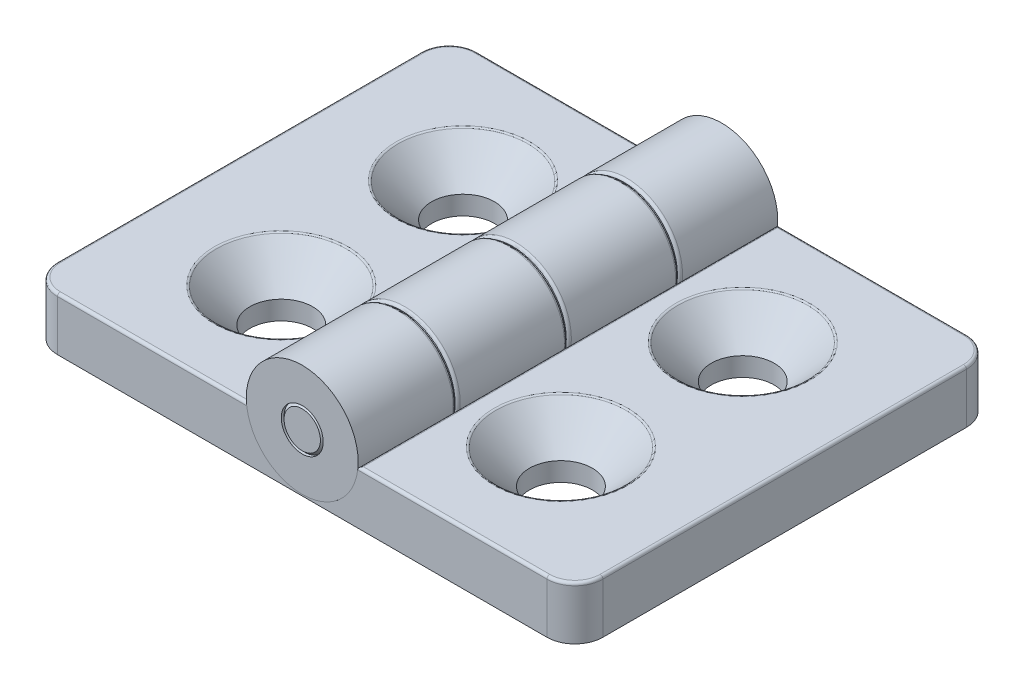
SolidWorks part; units mm, degrees
ref_plane "前视基准面" through (0, 0, 0) normal (0, 0, 1) x (1, 0, 0)
ref_plane "上视基准面" through (0, 0, 0) normal (0, 1, 0) x (1, 0, 0)
ref_plane "右视基准面" through (0, 0, 0) normal (1, 0, 0) x (0, 0, -1)
sketch "草图1" plane through (0, 0, 0) normal (0, 0, 1) x (1, 0, 0)
  circle A0 centre (0, 0) radius 4
  circle A1 centre (0, 0) radius 1.5
  dimension "D1" = 8
  dimension "D2" = 3
extrude "凸台-拉伸1" add sketch "草图1" along normal mid plane 30
sketch "草图2" plane through (0, 0, 0) normal (0, 0, 1) x (1, 0, 0)
  circle A0 centre (0, 0) radius 1.5
  dimension "D1" = 3
extrude "凸台-拉伸2" add sketch "草图2" along normal mid plane 30 separate body
chamfer "倒角1" distance 0.2 angle 45 1 edges at (1.5, 0, 15)
sketch "草图3" plane through (0, 0, 0) normal (0, 1, 0) x (1, 0, 0)
  line L0 (0, 0) -> (14.2235, 0) construction
  line L1 (3.8325, 8) -> (4.8947, 8)
  line L2 (3.8325, 8) -> (3.8325, 7.9)
  line L3 (3.8325, 7.9) -> (4.8947, 7.9)
  line L4 (4.8947, 8) -> (4.8947, 7.9)
  line L5 (4, 15) -> (-4, 15) construction
  line L6 (-4, -15) -> (4, -15) construction
  line L9 (3.8325, 0.05) -> (4.8947, 0.05)
  line L10 (3.8325, 0.05) -> (3.8325, -0.05)
  line L11 (3.8325, -0.05) -> (4.8947, -0.05)
  line L12 (4.8947, 0.05) -> (4.8947, -0.05)
  line L13 (3.8325, -7.9) -> (4.8947, -7.9)
  line L14 (3.8325, -7.9) -> (3.8325, -8)
  line L15 (3.8325, -8) -> (4.8947, -8)
  line L16 (4.8947, -7.9) -> (4.8947, -8)
  point P4 (3.8325, 0)
  dimension "D1" = 7
  dimension "D2" = 0.1
  dimension "D3" = 7
revolve "切除-旋转1" cut sketch "草图3" angle 360 about axis through (0, 0, 15) along (0, 0, -1)
fillet "圆角1" radius 0.2 6 edges at (4, 0, 8) (-4, 0, 7.9) (4, 0, 0.05) (-4, 0, -0.05) (4, 0, -7.9) (-4, 0, -8)
sketch "草图4" plane through (0, 0, 0) normal (0, 1, 0) x (1, 0, 0)
  line L0 (-4, -15) -> (4, -15) construction
  line L1 (-19.5, 15) -> (19.5, 15)
  line L2 (-19.5, 15) -> (-19.5, -15)
  line L3 (-19.5, -15) -> (19.5, -15)
  line L4 (19.5, 15) -> (19.5, -15)
  line L5 (4, 15) -> (-4, 15) construction
  point P4 (0, -15)
  dimension "D1" = 39
sketch "草图5" plane through (0, 0, -15) normal (0, 0, -1) x (-1, 0, 0)
  line L0 (3.9887, -0.3) -> (19.5, -0.3)
  line L3 (-19.5, -0.3) -> (-3.9887, -0.3)
  line L4 (-19.5, -0.3) -> (-19.5, -4.1)
  line L5 (-19.5, -4.1) -> (19.5, -4.1)
  line L6 (19.5, -0.3) -> (19.5, -4.1)
  circle A0 centre (0, 0) radius 4 construction
  arc A1 (-3.9887, -0.3) -> (3.9887, -0.3) centre (0, 0) ccw
  dimension "D2" = 0.3
  dimension "D4" = 19.5
  dimension "D1" = 3.8
  dimension "D3" = 39
extrude "凸台-拉伸6" add sketch "草图5" against normal up to surface (30 mm away) separate body up to face at (4, 0, 15)
hole_wizard "M4 平头机械螺钉的锥形沉头孔1" positions "草图7" profile "草图6" countersink size "M4" standard "Ansi Metric" end condition through all
sketch "草图7" plane through (0, -0.3, 0) normal (0, 1, 0) x (-1, 0, 0)
  line L0 (0, 0) -> (0, 18.3669) construction
  line L2 (0, 0) -> (27.3768, 0) construction
  point P1 (10, -6.5)
  point P3 (-10, -6.5)
  point P5 (10, 6.5)
  point P7 (-10, 6.5)
  dimension "D1" = 20
  dimension "D2" = 13
sketch "草图6" plane through (-10, -0.3, -6.5) normal (1, 0, 0) x (0, 0, 1)
  line L0 (0, 0) -> (0, 3.8)
  line L1 (0, 3.8) -> (2.25, 3.8)
  line L2 (2.25, 3.8) -> (2.25, 2.45)
  line L3 (2.25, 2.45) -> (4.7, 0)
  line L5 (4.7, 0) -> (0, 0)
  line L6 (-2.25, 2.45) -> (-4.7, 0) construction
  line L11 (0, -6.35) -> (0, 107.95) construction
  dimension "通孔孔直径" = 4.5
  dimension "通孔孔深度" = 3.8
  dimension "近端锥形沉头孔直径" = 9.4
  dimension "近端锥形沉头孔角度" = 90
fillet "圆角2" radius 0.2 12 edges at (11.7444, -0.3, -15) (19.5, -0.3, 0) (11.7444, -0.3, 15) (3.9887, -0.3, 0) (10, -0.3, 11.2) (10, -0.3, -1.8) (-11.7444, -0.3, -15) (-3.9887, -0.3, 0) (-11.7444, -0.3, 15) (-19.5, -0.3, 0) (-10, -0.3, 11.2) (-10, -0.3, -1.8)
fillet "圆角3" radius 2 8 edges at (-19.4414, -0.3586, -14.9414) (19.4414, -0.3586, -14.9414) (19.4414, -0.3586, 14.9414) (-19.4414, -0.3586, 14.9414) (-19.5, -2.3, 15) (19.5, -2.3, 15) (19.5, -2.3, -15) (-19.5, -2.3, -15)
chamfer "倒角2" distance 0.5 angle 45 1 edges at (1.5, 0, -15)
